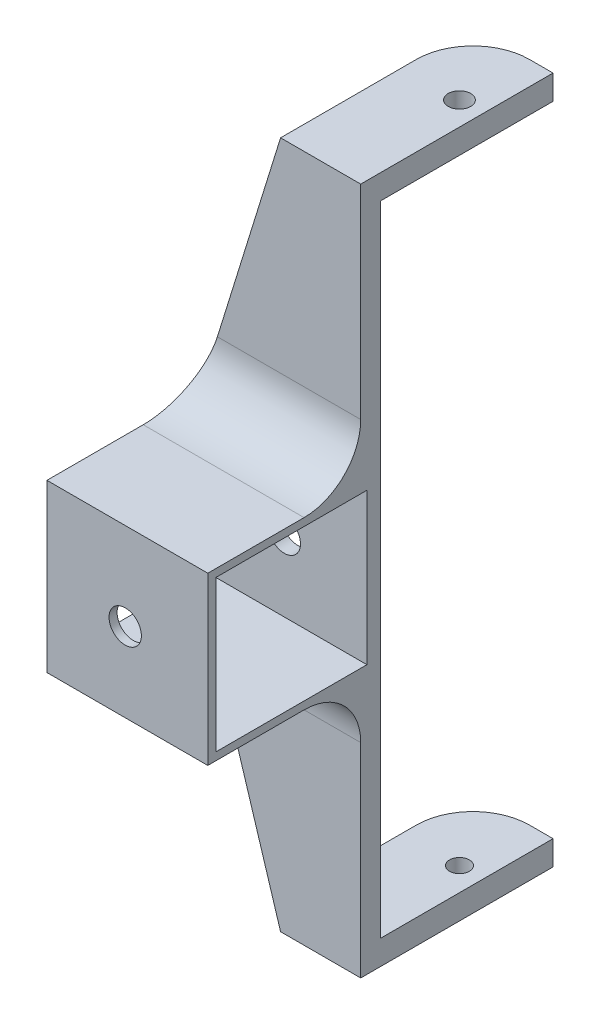
SolidWorks part; units mm, degrees
ref_plane "Front Plane" through (0, 0, 0) normal (0, 0, 1) x (1, 0, 0)
ref_plane "Top Plane" through (0, 0, 0) normal (0, 1, 0) x (1, 0, 0)
ref_plane "Right Plane" through (0, 0, 0) normal (1, 0, 0) x (0, 0, -1)
sketch "Sketch2" plane through (0, 0, 0) normal (0, 0, 1) x (1, 0, 0)
  line L7 (62.4862, 19.4928) -> (62.4862, -9.9072)
  line L8 (62.4862, -9.9072) -> (34.0822, -9.9072)
  line L9 (34.0822, 19.4928) -> (34.0822, -9.9072)
  line L10 (62.4862, 19.4928) -> (34.0822, 19.4928)
  line L11 (892.7838, 17.4928) -> (-250.2162, 17.4928) construction
  line L12 (892.7838, -7.9072) -> (-250.2162, -7.9072) construction
  dimension "D1" = 2
  dimension "D2" = 2
extrude "Boss-Extrude1" add sketch "Sketch2" along normal blind 30.48
sketch "Sketch5" plane through (0, 0, 0) normal (0, 0, -1) x (-1, 0, 0)
  line L0 (-62.4862, 19.4928) -> (-62.4862, 65.4928)
  line L1 (-62.4862, 65.4928) -> (-48.3347, 65.4928)
  line L2 (-48.3347, 65.4928) -> (-34.0822, 19.4928)
  line L3 (-34.0822, 19.4928) -> (-62.4862, 19.4928)
  dimension "D1" = 46
extrude "Boss-Extrude2" add sketch "Sketch5" against normal blind 3.48
ref_axis "Axis2" through (34.0822, 4.7928, 30.48) along (1, 0, 0)
ref_plane "Plane1" through (0, 4.7928, 0) normal (0, -1, 0) x (1, 0, 0)
sketch "Sketch7" plane through (0, 0, 0) normal (0, 0, -1) x (-1, 0, 0)
  line L0 (-62.4862, -9.9072) -> (-62.4862, 65.4928) construction
  line L1 (-62.4862, 61.1667) -> (-48.3347, 61.1667)
  line L2 (-62.4862, 61.1667) -> (-62.4862, 65.4928)
  line L3 (-62.4862, 65.4928) -> (-48.3347, 65.4928)
  line L4 (-48.3347, 61.1667) -> (-48.3347, 65.4928)
  line L5 (137.412, 61.1667) -> (-74.088, 61.1667) construction
extrude "Boss-Extrude3" add sketch "Sketch7" along normal blind 30.48
sketch "Sketch8" plane through (0, 65.4928, 0) normal (0, 1, 0) x (1, 0, 0)
  circle A1 centre (58.338, 18.1) radius 1.9869
extrude "Cut-Extrude3" cut sketch "Sketch8" against normal blind 4.48
fillet "Fillet2" radius 10 1 edges at (48.2842, 19.4928, 3.48)
mirror "Mirror3" about plane through (0, 4.7928, 0) normal (0, -1, 0) of "Boss-Extrude1", "Boss-Extrude3", "Boss-Extrude2"
sketch "Sketch4" plane through (0, 0, 30.48) normal (0, 0, 1) x (1, 0, 0)
  circle A0 centre (47.9025, 4.0545) radius 2.8565
extrude "Cut-Extrude2" cut sketch "Sketch4" against normal blind 30.48
fillet "Fillet3" radius 10 1 edges at (48.2842, -9.9072, 3.48)
sketch "Sketch9" plane through (0, -55.9072, 0) normal (0, -1, 0) x (1, 0, 0)
  circle A1 centre (58.338, -18.1) radius 1.75
extrude "Cut-Extrude4" cut sketch "Sketch9" against normal blind 4.48
sketch "Sketch3" plane through (62.4862, 0, 0) normal (1, 0, 0) x (0, 0, -1)
  line L1 (-2.39, 18.1278) -> (-29.06, 18.1278)
  line L2 (-2.39, 18.1278) -> (-2.39, -8.5422)
  line L3 (-2.39, -8.5422) -> (-29.06, -8.5422)
  line L4 (-29.06, 18.1278) -> (-29.06, -8.5422)
  dimension "D1" = 26.67
extrude "Cut-Extrude1" cut sketch "Sketch3" against normal blind 30.48
fillet "Fillet4" radius 10 2 edges at (48.3347, 63.3298, -30.48) (48.3347, -53.7441, -30.48)
